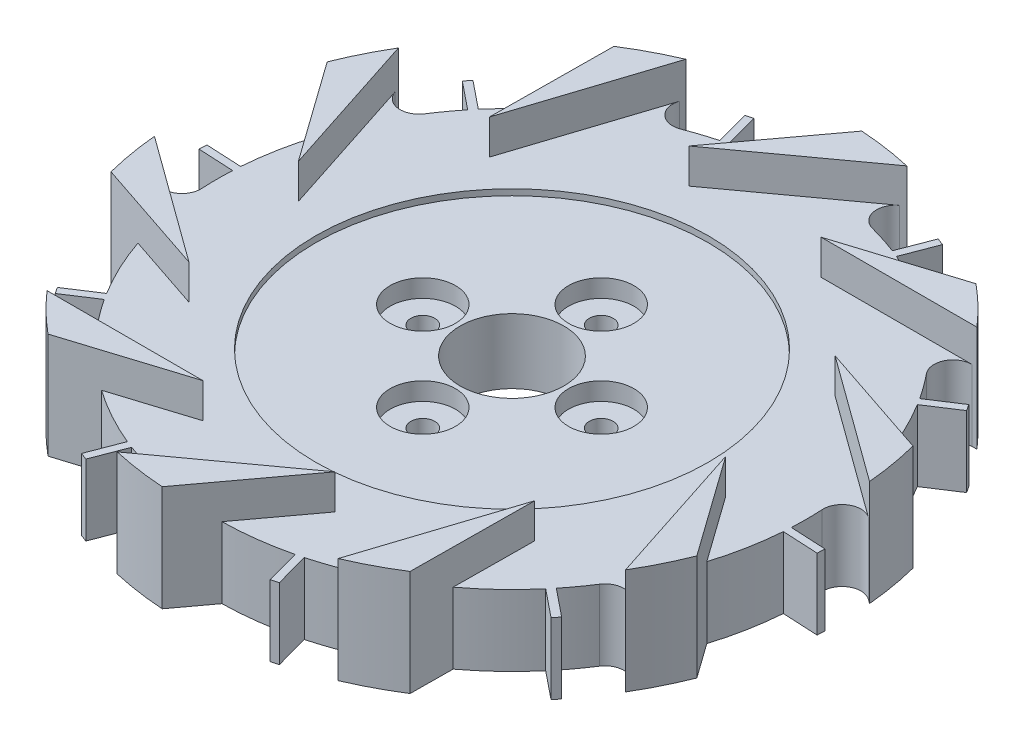
SolidWorks part; units mm, degrees
material "6061-T6 (SS)"
ref_plane "Front Plane" through (0, 0, 0) normal (0, 0, 1) x (1, 0, 0)
ref_plane "Top Plane" through (0, 0, 0) normal (0, 1, 0) x (1, 0, 0)
ref_plane "Right Plane" through (0, 0, 0) normal (1, 0, 0) x (0, 0, -1)
sketch "Sketch1" plane through (0, 0, 0) normal (1, 0, 0) x (0, 0, -1)
  line L0 (0, 26.2631) -> (0, -3.7705) construction
  line L1 (0, -3.7705) -> (-49.53, -3.7705)
  line L2 (-49.53, -3.7705) -> (-49.53, 8.1675)
  line L3 (-33.0001, 8.1675) -> (-49.53, 8.1675)
  line L4 (-33.0001, 8.1675) -> (-33.0001, 7.1515)
  line L5 (-33.0001, 7.1515) -> (0, 7.1515)
  line L6 (0, 7.1515) -> (0, -3.7705)
  dimension "D1" = 33.0001
  dimension "D2" = 49.53
  dimension "D3" = 1.016
  dimension "D4" = 11.938
revolve "Revolve1" add sketch "Sketch1" angle 360 about L0
sketch "Sketch2" plane through (0, 8.1675, 0) normal (0, 1, 0) x (1, 0, 0)
  line L8 (15.5361, 36.4236) -> (41.7488, 36.4236) construction
  line L10 (15.5361, 36.4236) -> (41.7488, 36.4236)
  line L11 (15.5361, 36.4236) -> (35.342, 42.6684)
  circle A0 centre (0, 0) radius 39.5986 construction
  circle A3 centre (0, 0) radius 55.4044 construction
  circle A5 centre (0, 0) radius 33.0001 construction
  arc A6 (41.7488, 36.4236) -> (35.342, 42.6684) centre (0, 0) ccw
  point P9 (-2.4416, -40.4611)
  dimension "D1" = 66.0001
  dimension "D2" = 36.4236
  dimension "D4" = 17.5
  dimension "D3" = 79.1972
extrude "Boss-Extrude1" add sketch "Sketch2" along normal blind 5.842 and the other way blind 11.938
pattern_circular "CirPattern1" count 10 over 360 about axis through (0, 8.1675, 0) along (0, 1, 0) of "Boss-Extrude1"
ref_plane "Plane1" through (-49.4669, -3.7705, -2.4996) normal (-0.9987, 0, -0.0505) x (-0.0505, 0, 0.9987)
sketch "Sketch3" plane through (-49.4669, -3.7705, -2.4996) normal (-0.9987, 0, -0.0505) x (-0.0505, 0, 0.9987)
  line L22 (-1.27, 0) -> (-1.27, 11.938)
  line L23 (-12.1773, 0) -> (12.1773, 0) construction
  line L24 (12.1773, 11.938) -> (-12.1773, 11.938) construction
  line L25 (-1.27, 11.938) -> (0, 11.938)
  line L26 (12.1773, 11.938) -> (1.5252, 11.938) construction
  line L27 (0, 11.938) -> (0, 0)
  line L28 (0, 0) -> (-1.27, 0)
  line L29 (-12.1773, 0) -> (12.1773, 0) construction
  point P12 (0, 0)
  dimension "D1" = 1.27
  dimension "D2" = 0
extrude "Boss-Extrude2" add sketch "Sketch3" along normal blind 5.969 and the other way up to next
pattern_circular "CirPattern16" count 10 over 360 about axis through (0, 8.1675, 0) along (0, 1, 0) of "Boss-Extrude2"
sketch "Sketch4" plane through (0, 7.1515, 0) normal (0, 1, 0) x (1, 0, 0)
  circle A0 centre (0, 0) radius 8.7312
  dimension "D1" = 17.4625
extrude "Cut-Extrude1" cut sketch "Sketch4" against normal up to next
sketch "Sketch5" plane through (0, -3.7705, 0) normal (0, -1, 0) x (-1, 0, 0)
  circle A0 centre (0, 0) radius 44.45
  dimension "D1" = 88.9
extrude "Cut-Extrude2" cut sketch "Sketch5" against normal blind 6.35
sketch "Sketch6" plane through (0, 2.5795, 0) normal (0, -1, 0) x (1, 0, 0)
  circle A0 centre (0, 0) radius 19.05
  circle A1 centre (0, 0) radius 8.7312 construction
  circle A2 centre (0, 0) radius 8.7312
  dimension "D1" = 38.1
extrude "Boss-Extrude3" add sketch "Sketch6" along normal up to surface (6.35 mm away) up to face at (0, -3.7705, -44.45)
sketch "Sketch9" plane through (0, 7.1515, 0) normal (0, 1, 0) x (1, 0, 0)
  circle A0 centre (0, 15) radius 2
  dimension "D1" = 4
  dimension "D2" = 15
extrude "Cut-Extrude3" cut sketch "Sketch9" against normal up to next
pattern_circular "CirPattern17" count 4 over 360 about axis through (0, 7.1515, 0) along (0, 1, 0) of "Cut-Extrude3"
ref_plane "Plane2" through (0, 0, 50.8) normal (0, 0, 1) x (1, 0, 0)
sketch "Sketch15" plane through (0, 7.1515, 0) normal (0, 1, 0) x (1, 0, 0)
  circle A0 centre (0, 15) radius 5.5
  circle A1 centre (15, 0) radius 5.5
  circle A2 centre (0, -15) radius 5.5
  circle A3 centre (-15, 0) radius 5.5
  dimension "D1" = 11
extrude "Cut-Extrude4" cut sketch "Sketch15" against normal blind 3
ref_plane "Plane4" through (-49.53, 0, 0) normal (1, 0, 0) x (0, 0, -1)
sketch "Sketch16" plane through (-49.4669, -3.7705, -2.4996) normal (0.9987, 0, 0.0505) x (0.0505, 0, -0.9987)
  line L4 (4.0496, 0) -> (10.3996, 0)
  line L6 (10.3996, 0) -> (10.3996, 3.175)
  line L13 (4.0496, 0) -> (4.0496, 3.175)
  arc A0 (10.3996, 3.175) -> (4.0496, 3.175) centre (7.2246, 3.175) ccw
  dimension "D2" = 3.175
  dimension "D1" = 6.35
extrude "Cut-Extrude5" cut sketch "Sketch16" against normal blind 7.366 and the other way up to next
fillet "Fillet2" radius 3.175 10 edges at (48.5631, 2.1985, -9.7389) (33.564, 2.1985, -36.4236) (5.7446, 2.1985, -49.1957) (-45.0127, 2.1985, -20.6658) (-24.2691, 2.1985, -43.1768) (-48.5631, 2.1985, 9.7389) (-33.564, 2.1985, 36.4236) (-5.7446, 2.1985, 49.1957) (24.2691, 2.1985, 43.1768) (45.0127, 2.1985, 20.6658)
sketch "Sketch20" plane through (0, 14.0095, 0) normal (0, 1, 0) x (1, 0, 0)
  circle A0 centre (34.6551, 38.9968) radius 1.8986 construction
  dimension "D1" = 3.7973
sketch "Sketch17" [suppressed] plane through (0, 8.1675, 0) normal (0, 1, 0) x (1, 0, 0)
  line L0 (0, 36.4236) -> (-21.4093, 29.4673) construction
ref_plane "Plane5" through (15.5361, 8.1675, -36.4236) normal (1, 0, 0) x (0, 0, -1)
sketch "Sketch19" plane through (0, 0, 0) normal (1, 0, 0) x (0, 0, -1)
  line L0 (-2.6691, 14.0095) -> (-2.6691, 8.1675)
  line L1 (-3.6469, 14.0095) -> (11.2555, 14.0095) construction
  line L2 (-2.6691, 8.1675) -> (-39.5986, 8.1675)
  line L3 (-39.5986, 8.1675) -> (-39.5986, 14.0095)
  line L4 (-39.5986, 14.0095) -> (-2.6691, 14.0095)
  line L5 (0, 14.7444) -> (0, 13.7821) construction
  dimension "D1" = 5.842
  dimension "D2" = 39.5986
revolve "Cut-Revolve1" [suppressed] cut sketch "Sketch19" angle 360 about L5
